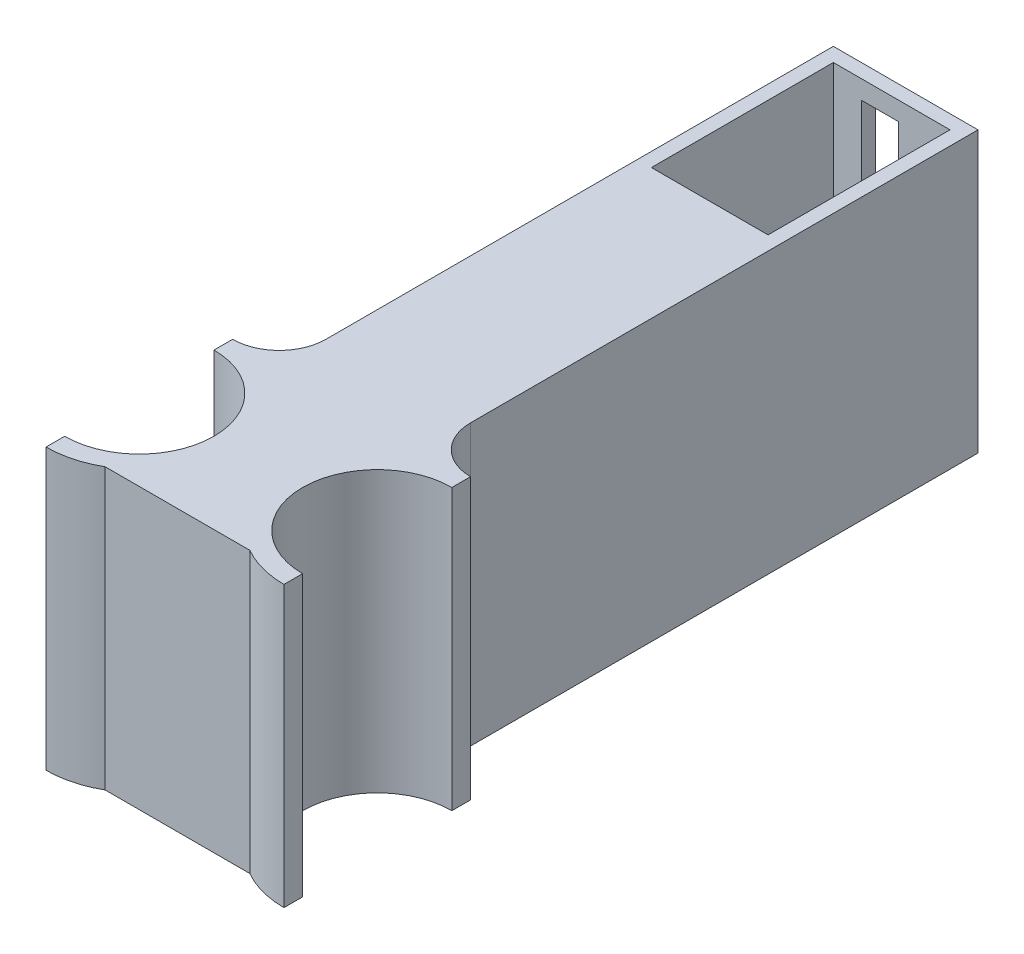
SolidWorks part; units mm, degrees
ref_plane "Front Plane" through (0, 0, 0) normal (0, 0, 1) x (1, 0, 0)
ref_plane "Top Plane" through (0, 0, 0) normal (0, 1, 0) x (1, 0, 0)
ref_plane "Right Plane" through (0, 0, 0) normal (1, 0, 0) x (0, 0, -1)
sketch "Sketch1" plane through (0, 0, 0) normal (0, 1, 0) x (1, 0, 0)
  line L0 (-15.5, 22.5) -> (15.5, 22.5)
  line L1 (-12.5, 19.5) -> (12.5, 19.5)
  line L2 (-12.5, 19.5) -> (-12.5, -19.5)
  line L3 (-12.5, -19.5) -> (12.5, -19.5)
  line L4 (12.5, 19.5) -> (12.5, -19.5)
  line L5 (-12.5, 19.5) -> (12.5, -19.5) construction
  line L6 (-12.5, -19.5) -> (12.5, 19.5) construction
  line L7 (15.5, 22.5) -> (15.5, -22.5)
  line L8 (-15.5, -22.5) -> (15.5, -22.5)
  line L9 (-15.5, 22.5) -> (-15.5, -22.5)
  point P0 (0, 0)
  dimension "D1" = 25
  dimension "D2" = 39
  dimension "D3" = 3
extrude "Boss-Extrude1" add sketch "Sketch1" along normal blind 60
sketch "Sketch5" plane through (0, 60, 0) normal (0, 1, 0) x (1, 0, 0)
  line L1 (-15.5, -133.5779) -> (15.5, -133.5779)
  line L5 (-15.5, -22.5) -> (15.5, -22.5)
  line L6 (0, -24.75) -> (0, 24.75) construction
  line L7 (-15.5, -22.5) -> (15.5, -22.5)
  line L8 (-15.5, -22.5) -> (-15.5, -98.9369)
  line L10 (15.5, -22.5) -> (15.5, -98.9369)
  line L14 (-25.5, -136.2574) -> (-25.5, -132.2574)
  line L15 (-25.5, -100.2574) -> (-25.5, -96.2574)
  line L17 (25.5, -136.2574) -> (25.5, -132.2574)
  line L18 (25.5, -100.2574) -> (25.5, -96.2574)
  arc A5 (-25.5, -132.2574) -> (-25.5, -100.2574) centre (-25.5, -116.2574) ccw
  arc A6 (-25.5, -136.2574) -> (-15.5, -133.5779) centre (-25.5, -116.2574) ccw
  arc A7 (-15.5, -98.9369) -> (-25.5, -96.2574) centre (-25.5, -116.2574) ccw
  arc A8 (25.5, -136.2574) -> (15.5, -133.5779) centre (25.5, -116.2574) cw
  arc A9 (15.5, -98.9369) -> (25.5, -96.2574) centre (25.5, -116.2574) cw
  arc A10 (25.5, -132.2574) -> (25.5, -100.2574) centre (25.5, -116.2574) cw
  point P0 (15.5, -142.5)
  point P2 (15.5, -142.5)
  point P13 (0, -22.5)
  point P14 (23.9076, -138.1907)
  point P17 (14.3446, -141.1144)
  dimension "D4" = 31
  dimension "D3" = 32
  dimension "D5" = 40
  dimension "D6" = 10
extrude "Boss-Extrude3" add sketch "Sketch5" against normal blind 60
sketch "Sketch3" plane through (0, 0, -22.5) normal (0, 0, -1) x (-1, 0, 0)
  line L0 (-1.5, 56) -> (-1.5, 4)
  line L1 (17.05, 0) -> (-17.05, 0) construction
  line L3 (6.5, 56) -> (6.5, 4)
  line L4 (-1.5, 56) -> (6.5, 56)
  line L5 (-1.5, 4) -> (6.5, 4)
  line L6 (15.5, 60) -> (15.5, 0) construction
  line L8 (-15.5, 60) -> (15.5, 60) construction
  dimension "D1" = 9
  dimension "D2" = 4
  dimension "D3" = 4
  dimension "D4" = 8
extrude "Cut-Extrude1" cut sketch "Sketch3" against normal blind 9
fillet "Fillet1" radius 10 2 edges at (-15.5, 30, 98.9369) (15.5, 30, 98.9369)
